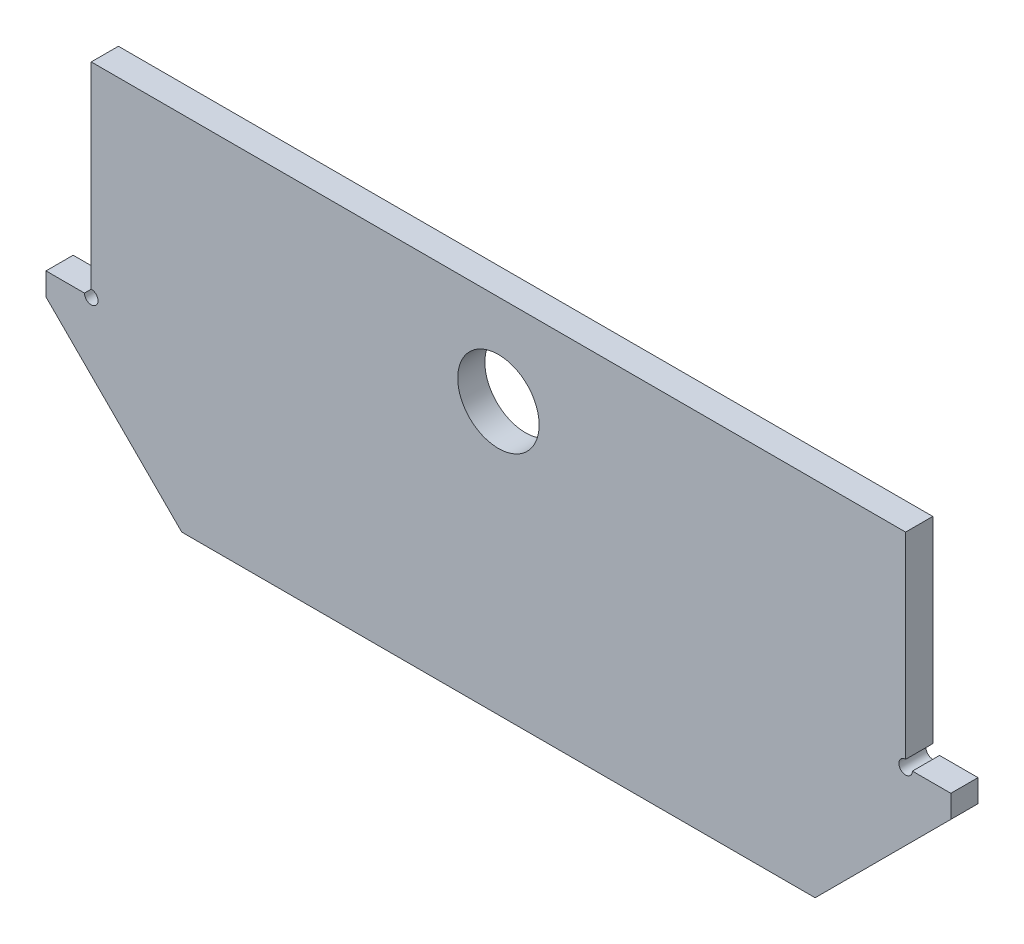
SolidWorks part; units mm, degrees
material "Plain Carbon Steel"
ref_plane "Front Plane" through (0, 0, 0) normal (0, 0, 1) x (1, 0, 0)
ref_plane "Top Plane" through (0, 0, 0) normal (0, 1, 0) x (1, 0, 0)
ref_plane "Right Plane" through (0, 0, 0) normal (1, 0, 0) x (0, 0, -1)
sketch "Sketch1" plane through (0, 0, 0) normal (0, 0, 1) x (1, 0, 0)
  line L0 (90, -1414) -> (90, -1289) construction
  line L2 (-90, -1414) -> (-90, -1369)
  line L3 (-90, -1369) -> (90, -1369)
  line L4 (90, -1414) -> (90, -1369)
  line L5 (686, -1414) -> (-686, -1414) construction
  line L6 (165, -1414) -> (165, -1289) construction
  line L7 (-100, -1414) -> (-90, -1414)
  line L8 (-100, -1414) -> (-100, -1419)
  line L9 (-70, -1449) -> (70, -1449)
  line L10 (100, -1414) -> (100, -1419)
  line L11 (90, -1414) -> (100, -1414)
  line L12 (-100, -1419) -> (-70, -1449)
  line L13 (70, -1449) -> (100, -1419)
  line L14 (-30.8239, -1354) -> (30.8239, -1354) construction
  line L15 (-90, -1409) -> (-90, -1294) construction
  point P10 (100, -1449)
  point P11 (-100, -1449)
  dimension "D1" = 80
  dimension "D2" = 15
  dimension "D3" = 200
extrude "Boss-Extrude1" add sketch "Sketch1" along normal blind 3 and the other way blind 3
sketch "Sketch2" plane through (0, 0, 3) normal (0, 0, 1) x (1, 0, 0)
  circle A1 centre (0, -1389) radius 9
  dimension "D1" = 18
extrude "Cut-Extrude1" cut sketch "Sketch2" against normal through all both and the other way through all
sketch "Sketch3" plane through (0, 0, 3) normal (0, 0, 1) x (1, 0, 0)
  circle A0 centre (-90, -1414) radius 1.5
  circle A1 centre (90, -1414) radius 1.5
  dimension "D1" = 3
  dimension "D2" = 3
extrude "Cut-Extrude2" cut sketch "Sketch3" against normal through all both and the other way through all
